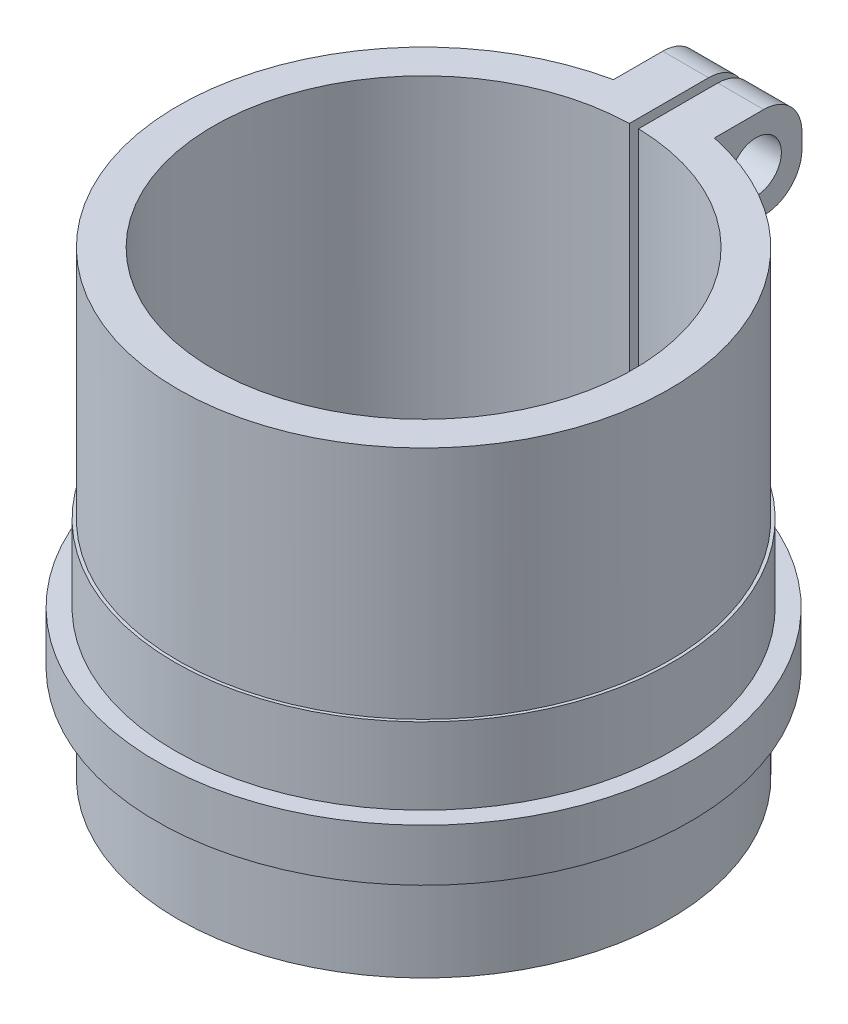
SolidWorks part; units mm, degrees
ref_plane "Front Plane" through (0, 0, 0) normal (0, 0, 1) x (1, 0, 0)
ref_plane "Top Plane" through (0, 0, 0) normal (0, 1, 0) x (1, 0, 0)
ref_plane "Right Plane" through (0, 0, 0) normal (1, 0, 0) x (0, 0, -1)
sketch "Sketch1" plane through (0, 0, 0) normal (0, 1, 0) x (1, 0, 0)
  circle A0 centre (0, 0) radius 20.6375
  circle A1 centre (0, 0) radius 17.4625
  dimension "D1" = 41.275
  dimension "D2" = 34.925
extrude "Boss-Extrude1" add sketch "Sketch1" along normal blind 38.1
ref_plane "Plane1" through (0, 7.9248, 0) normal (0, -1, 0) x (-1, 0, 0)
sketch "Sketch2" plane through (0, 7.9248, 0) normal (0, -1, 0) x (-1, 0, 0)
  circle A0 centre (0, 0) radius 20.6375 construction
  circle A1 centre (0, 0) radius 20.6375
  circle A2 centre (0, 0) radius 22.1615
  dimension "D1" = 1.524
extrude "Boss-Extrude2" add sketch "Sketch2" against normal blind 4.318
sketch "Sketch3" plane through (0, 0, 0) normal (0, -1, 0) x (1, 0, 0)
  circle A0 centre (0, 0) radius 20.3835
  circle A1 centre (0, 0) radius 20.6375 construction
  circle A2 centre (0, 0) radius 20.6375
  dimension "D1" = 0.254
extrude "Cut-Extrude1" cut sketch "Sketch3" against normal up to surface (7.9248 mm away) up to face at (0, 7.9248, -20.6375)
extrude "Cut-Extrude2" cut sketch "Sketch3<2>" along normal offset from surface (19.5072 mm away) 6.35 from surface up to face at (0, 12.2428, -20.6375) starting at face at (0, 38.1, 20.6375)
sketch "Sketch3<2>" plane through (0, 0, 0) normal (0, -1, 0) x (1, 0, 0) same geometry as "Sketch3"
sketch "Sketch4" plane through (0, 38.1, 0) normal (0, 1, 0) x (1, 0, 0)
  line L1 (-0.381, 17.4583) -> (0.381, 17.4583)
  line L2 (-0.381, 17.4583) -> (-0.381, 22.1615)
  line L3 (-0.381, 22.1615) -> (0.381, 22.1615)
  line L4 (0.381, 17.4583) -> (0.381, 22.1615)
  line L5 (-0.381, 17.4583) -> (0.381, 22.1615) construction
  line L6 (-0.381, 22.1615) -> (0.381, 17.4583) construction
  circle A0 centre (0, 0) radius 17.4625 construction
  circle A1 centre (0, 0) radius 22.1615 construction
  point P0 (0, 19.8099)
  dimension "D1" = 0.762
extrude "Cut-Extrude3" cut sketch "Sketch4" against normal blind 19.05
sketch "Sketch5" plane through (0.381, 0, 0) normal (-1, 0, 0) x (0, 0, 1)
  line L1 (-17.4583, 38.1) -> (-27.2154, 38.1)
  line L2 (-17.4583, 38.1) -> (-17.4583, 30.48)
  line L3 (-17.4583, 30.48) -> (-27.2154, 30.48)
  line L4 (-27.2154, 38.1) -> (-27.2154, 30.48)
  line L5 (-21.3847, 37.79) -> (-25.4261, 37.79) construction
  line L6 (-25.4261, 37.79) -> (-27.4468, 34.29) construction
  line L7 (-27.4468, 34.29) -> (-25.4261, 30.79) construction
  line L8 (-25.4261, 30.79) -> (-21.3847, 30.79) construction
  line L9 (-21.3847, 30.79) -> (-19.3639, 34.29) construction
  line L10 (-19.3639, 34.29) -> (-21.3847, 37.79) construction
  line L11 (-23.4054, 34.29) -> (-23.4054, 38.1) construction
  line L12 (-23.4054, 34.29) -> (-23.4054, 30.48) construction
  line L13 (-23.4054, 34.29) -> (-27.2154, 34.29) construction
  line L14 (-20.3799, 19.05) -> (-20.3799, 38.1) construction
  circle A0 centre (-23.4054, 34.29) radius 2.1
  circle A1 centre (-23.4054, 34.29) radius 3.5 construction
  circle A2 centre (-23.4054, 34.29) radius 3.5 construction
  dimension "D1" = 4.2
  dimension "D3" = 7
  dimension "D2" = 3.81
  dimension "D4" = 1.016
extrude "Boss-Extrude3" add sketch "Sketch5" against normal blind 3.81
mirror "Mirror1" about plane through (0, 0, 0) normal (1, 0, 0) of "Boss-Extrude3"
fillet "Fillet1" radius 3.175 4 edges at (-2.286, 30.48, -27.2154) (2.286, 30.48, -27.2154) (2.286, 38.1, -27.2154) (-2.286, 38.1, -27.2154)
